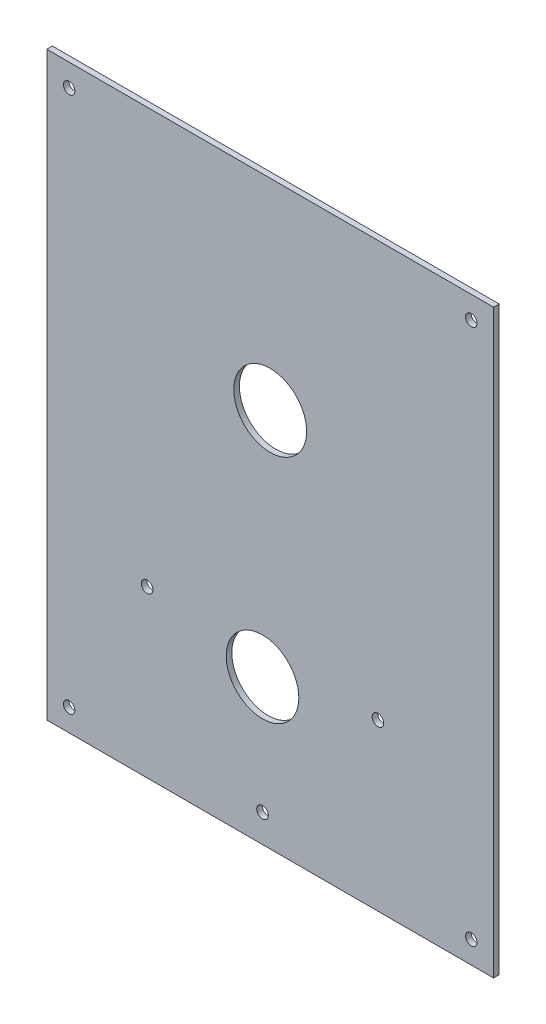
SolidWorks part; units mm, degrees
ref_plane "Front Plane" through (0, 0, 0) normal (0, 0, 1) x (1, 0, 0)
ref_plane "Top Plane" through (0, 0, 0) normal (0, 1, 0) x (1, 0, 0)
ref_plane "Right Plane" through (0, 0, 0) normal (1, 0, 0) x (0, 0, -1)
sketch "Sketch1" plane through (0, 0, 0) normal (0, 0, 1) x (1, 0, 0)
  line L0 (-107.0186, -211.0092) -> (146.9814, -211.0092)
  line L1 (146.9814, -211.0092) -> (146.9814, 119.1908)
  line L2 (146.9814, 119.1908) -> (-107.0186, 119.1908)
  line L3 (-107.0186, 119.1908) -> (-107.0186, -211.0092)
  circle A0 centre (19.9814, 4.8908) radius 20.701
  point P7 (19.9814, 119.1908)
  dimension "D3" = 41.402
  dimension "D1" = 254
  dimension "D2" = 330.2
  dimension "D4" = 114.3
extrude "Boss-Extrude1" add sketch "Sketch1" against normal blind 3.175
sketch "Sketch3" plane through (0, 0, 0) normal (0, 0, 1) x (1, 0, 0)
  line L0 (-107.0186, 119.1908) -> (-107.0186, -211.0092) construction
  line L1 (-50.0074, -116.8899) -> (15.6054, -128.4592) construction
  line L2 (-107.0186, -211.0092) -> (146.9814, -211.0092) construction
  line L3 (146.9814, -211.0092) -> (146.9814, 119.1908) construction
  line L4 (146.9814, 119.1908) -> (-107.0186, 119.1908) construction
  circle A0 centre (-50.0074, -116.8899) radius 3.3
  circle A1 centre (81.2182, -116.8899) radius 3.3
  circle A2 centre (15.6054, -195.0842) radius 3.3
  circle A3 centre (15.6054, -128.4592) radius 20.6375
  circle A4 centre (134.2814, 106.4908) radius 3.2512
  circle A5 centre (-94.3186, 106.4908) radius 3.2512
  circle A6 centre (134.2814, -198.3092) radius 3.2512
  circle A7 centre (-94.3186, -198.3092) radius 3.2512
  point P27 (0, 0)
  dimension "D1" = 6.6
  dimension "D2" = 6.6
  dimension "D3" = 6.6
  dimension "D4" = 41.275
  dimension "D9" = 6.5024
  dimension "D10" = 6.5024
  dimension "D11" = 6.5024
  dimension "D12" = 6.5024
  dimension "D5" = 122.624
  dimension "D6" = 82.55
  dimension "D7" = 12.7
  dimension "D8" = 12.7
  dimension "D13" = 12.7
  dimension "D14" = 12.7
extrude "Cut-Extrude2" cut sketch "Sketch3" against normal through all
